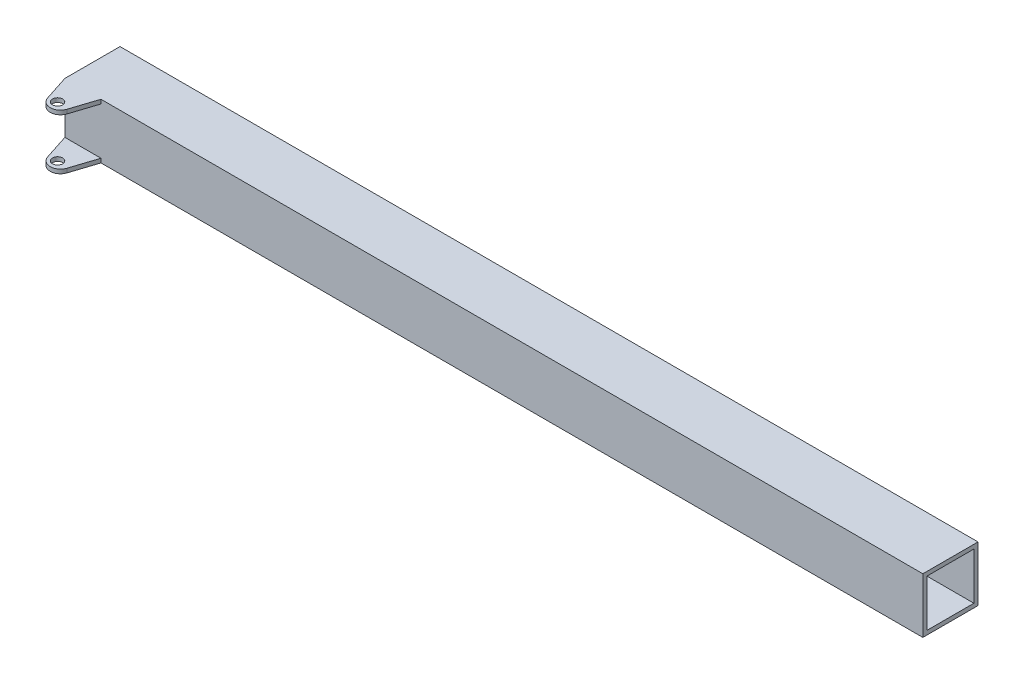
SolidWorks part; units mm, degrees
material "Plain Carbon Steel"
ref_plane "Front Plane" through (0, 0, 0) normal (0, 0, 1) x (1, 0, 0)
ref_plane "Top Plane" through (0, 0, 0) normal (0, 1, 0) x (1, 0, 0)
ref_plane "Right Plane" through (0, 0, 0) normal (1, 0, 0) x (0, 0, -1)
sketch "Sketch1" plane through (0, 0, 0) normal (1, 0, 0) x (0, 0, -1)
  line L1 (135, 270) -> (135, 0)
  line L3 (135, 0) -> (-135, 0)
  line L5 (-135, 270) -> (135, 270)
  line L6 (-135, 270) -> (-135, 0)
  line L7 (-135, 20) -> (-115, 20) construction
  line L8 (-115, 250) -> (115, 250)
  line L9 (-115, 250) -> (-115, 20)
  line L10 (-115, 20) -> (115, 20)
  line L11 (115, 250) -> (115, 20)
  line L12 (115, 250) -> (115, 270) construction
  line L13 (115, 250) -> (135, 250) construction
  line L14 (-115, 20) -> (-115, 0) construction
  dimension "D1" = 270
  dimension "D2" = 20
  dimension "D4" = 270
extrude "Boss-Extrude1" add sketch "Sketch1" against normal blind 4200
sketch "Sketch2" plane through (0, 0, 0) normal (0, -1, 0) x (1, 0, 0)
  line L0 (0, 135) -> (0, -135) construction
  circle A0 centre (-200, 0) radius 25
  dimension "D1" = 50
  dimension "D2" = 200
extrude "Boss-Extrude2" add sketch "Sketch2" against normal through all
sketch "Sketch3" plane through (0, 0, 0) normal (0, 1, 0) x (1, 0, 0)
  line L0 (-4023.2453, -135) -> (-4064.0768, -260.4725)
  line L1 (-4200, -135) -> (0, -135) construction
  line L2 (-4159.1684, -260.4725) -> (-4200, -135)
  line L3 (-4200, -135) -> (-4023.2453, -135)
  arc A1 (-4159.1684, -260.4725) -> (-4064.0768, -260.4725) centre (-4111.6226, -245) ccw
  circle A2 centre (-4118.2165, -252.56) radius 25
  point P7 (0, 0)
  point P8 (-4284.9634, -188.7063)
  point P13 (-4111.6226, -135)
  dimension "D1" = 50
  dimension "D3" = 50
  dimension "D2" = 110
  dimension "D4" = 117.56
extrude "Boss-Extrude3" add sketch "Sketch3" along normal blind 20
ref_plane "Plane1" through (0, 135, 0) normal (0, -1, 0) x (-1, 0, 0)
mirror "Mirror1" about plane through (0, 135, 0) normal (0, -1, 0) of "Boss-Extrude3"
